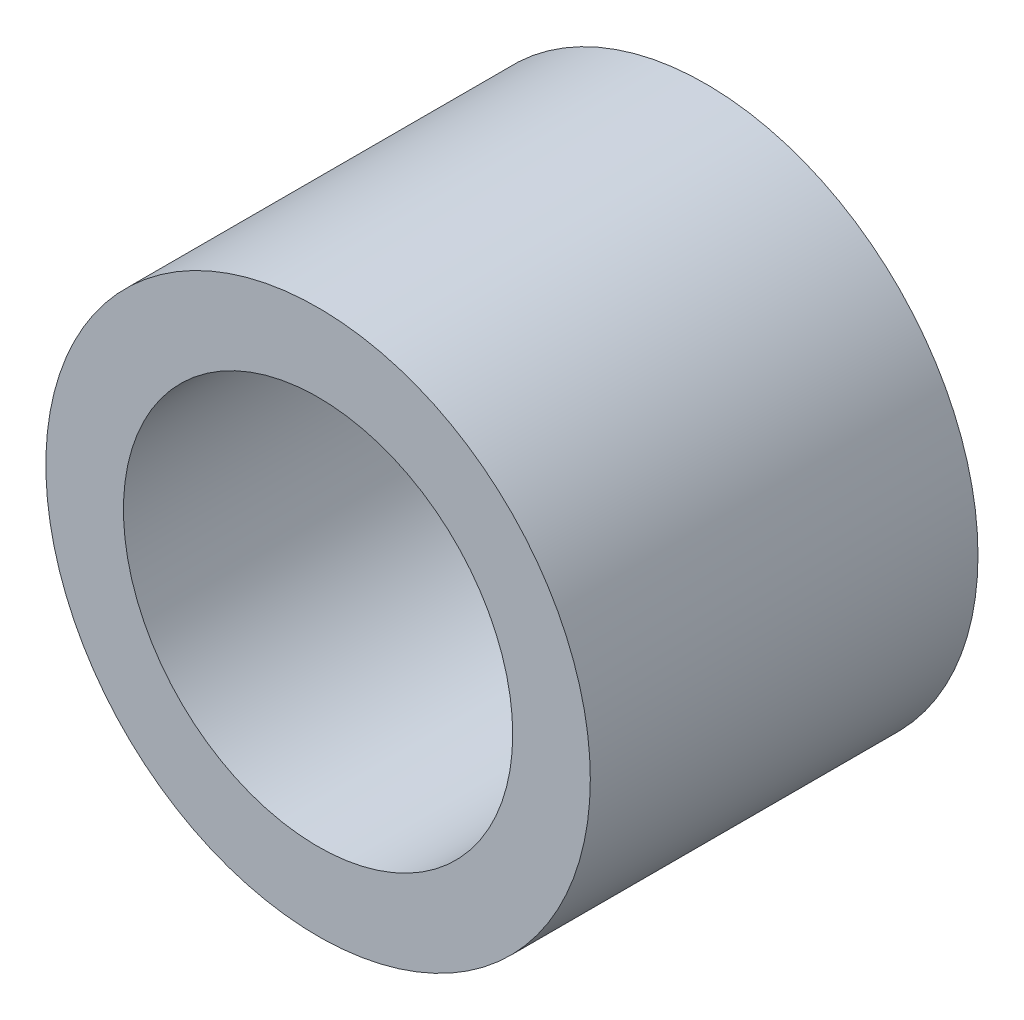
SolidWorks part; units mm, degrees
material "PET"
ref_plane "Front Plane" through (0, 0, 0) normal (0, 0, 1) x (1, 0, 0)
ref_plane "Top Plane" through (0, 0, 0) normal (0, 1, 0) x (1, 0, 0)
ref_plane "Right Plane" through (0, 0, 0) normal (1, 0, 0) x (0, 0, -1)
sketch "Sketch1" plane through (0, 0, 0) normal (0, 0, 1) x (1, 0, 0)
  circle A0 centre (0, 0) radius 3.9726
  circle A1 centre (0, 0) radius 5.5562
  dimension "D1" = 7.9451
  dimension "D2" = 11.1125
extrude "Boss-Extrude1" add sketch "Sketch1" along normal blind 7.9121
ref_axis "Axis1" through (0, 0, 7.9121) along (0, 0, -1)
